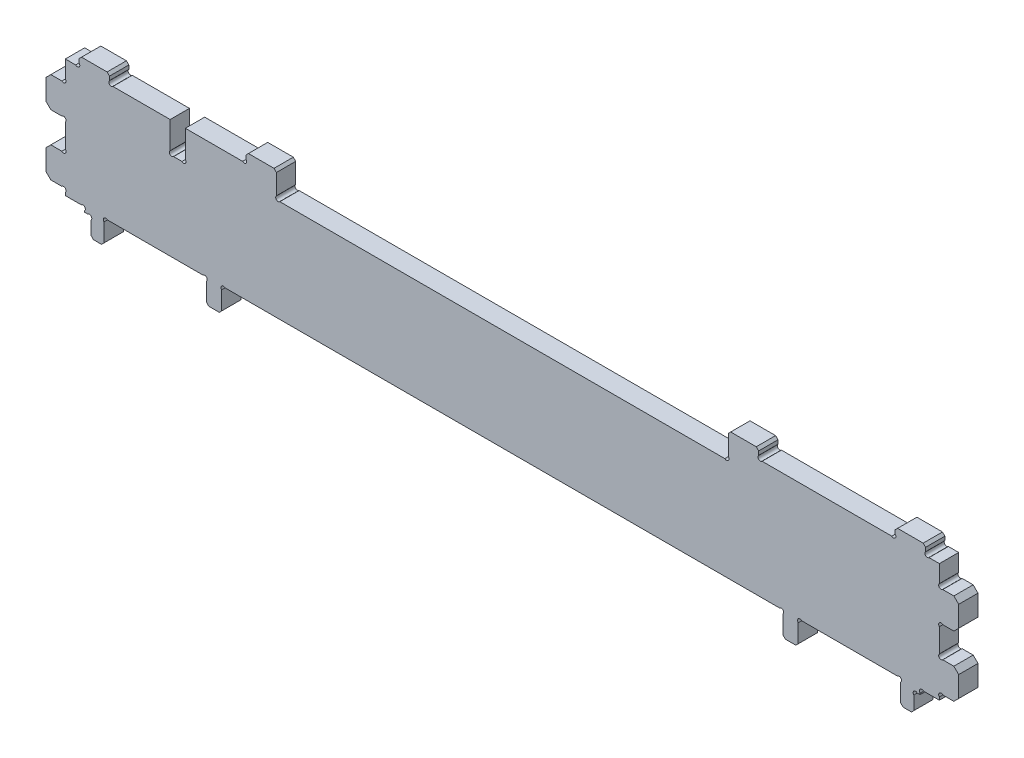
SolidWorks part; units mm, degrees
ref_plane "Front Plane" through (0, 0, 0) normal (0, 0, 1) x (1, 0, 0)
ref_plane "Top Plane" through (0, 0, 0) normal (0, 1, 0) x (1, 0, 0)
ref_plane "Right Plane" through (0, 0, 0) normal (1, 0, 0) x (0, 0, -1)
sketch "Sketch1" plane through (0, 0, 0) normal (0, 0, 1) x (1, 0, 0)
  line L69 (134.6215, -67.6125) -> (134.6215, -60.8103)
  line L70 (133.499, -59.6877) -> (102.0491, -59.6877)
  line L71 (100.9265, -60.8103) -> (100.9265, -67.6125)
  line L72 (100.9265, -67.6125) -> (95.9265, -67.6125)
  line L73 (95.9265, -67.6125) -> (95.9265, -60.8103)
  line L74 (94.804, -59.6877) -> (-87.4609, -59.6877)
  line L75 (-88.5835, -60.8103) -> (-88.5835, -67.6125)
  line L76 (-88.5835, -67.6125) -> (-93.5835, -67.6125)
  line L77 (-93.5835, -67.6125) -> (-93.5835, -60.8103)
  line L78 (-94.706, -59.6877) -> (-126.1559, -59.6877)
  line L79 (-127.2785, -60.8103) -> (-127.2785, -67.6125)
  line L80 (-127.2785, -67.6125) -> (-131.5077, -67.6125)
  line L81 (-131.5077, -67.6125) -> (-131.5077, -62.3851)
  line L82 (-132.6302, -61.2625) -> (-133.6285, -61.2625)
  line L83 (-133.6285, -61.2625) -> (-133.6285, -60.8103)
  line L84 (-134.751, -59.6877) -> (-139.9785, -59.6877)
  line L85 (-139.9785, -59.6877) -> (-139.9785, -58.7351)
  line L86 (-141.101, -57.6125) -> (-146.3285, -57.6125)
  line L87 (-146.3285, -57.6125) -> (-146.3285, -47.6125)
  line L88 (-146.3285, -47.6125) -> (-141.101, -47.6125)
  line L89 (-139.9785, -46.49) -> (-139.9785, -38.7351)
  line L90 (-141.101, -37.6125) -> (-146.3285, -37.6125)
  line L91 (-146.3285, -37.6125) -> (-146.3285, -27.6125)
  line L92 (-146.3285, -27.6125) -> (-141.101, -27.6125)
  line L93 (-139.9785, -26.49) -> (-139.9785, -20.7875)
  line L94 (-139.9785, -20.7875) -> (-136.576, -20.7875)
  line L95 (-135.4535, -19.665) -> (-135.4535, -17.6125)
  line L96 (-135.4535, -17.6125) -> (-125.4535, -17.6125)
  line L97 (-125.4535, -17.6125) -> (-125.4535, -19.665)
  line L98 (-124.3309, -20.7875) -> (-105.5215, -20.7875)
  line L99 (-105.5215, -20.7875) -> (-105.5215, -29.665)
  line L100 (-104.3989, -30.7875) -> (-101.644, -30.7875)
  line L101 (-100.5215, -29.665) -> (-100.5215, -20.7875)
  line L102 (-100.5215, -20.7875) -> (-81.712, -20.7875)
  line L103 (-80.5895, -19.665) -> (-80.5895, -17.6125)
  line L104 (-80.5895, -17.6125) -> (-70.5895, -17.6125)
  line L105 (-70.5895, -17.6125) -> (-70.5895, -24.1277)
  line L106 (-70.5895, -24.1277) -> (77.9325, -24.1277)
  line L107 (77.9325, -24.1277) -> (77.9325, -17.6125)
  line L108 (77.9325, -17.6125) -> (87.9325, -17.6125)
  line L109 (87.9325, -17.6125) -> (87.9325, -19.665)
  line L110 (89.0551, -20.7875) -> (131.674, -20.7875)
  line L111 (132.7965, -19.665) -> (132.7965, -17.6125)
  line L112 (132.7965, -17.6125) -> (142.7965, -17.6125)
  line L113 (142.7965, -17.6125) -> (142.7965, -19.665)
  line L114 (143.9191, -20.7875) -> (147.3215, -20.7875)
  line L115 (147.3215, -20.7875) -> (147.3215, -26.49)
  line L116 (148.4441, -27.6125) -> (153.6715, -27.6125)
  line L117 (153.6715, -27.6125) -> (153.6715, -37.6125)
  line L118 (153.6715, -37.6125) -> (148.4441, -37.6125)
  line L119 (147.3215, -38.7351) -> (147.3215, -46.49)
  line L120 (148.4441, -47.6125) -> (153.6715, -47.6125)
  line L121 (153.6715, -47.6125) -> (153.6715, -57.6125)
  line L122 (153.6715, -57.6125) -> (148.4441, -57.6125)
  line L123 (147.3215, -58.7351) -> (147.3215, -59.6877)
  line L124 (147.3215, -59.6877) -> (142.0941, -59.6877)
  line L125 (140.9715, -60.8103) -> (140.9715, -61.2625)
  line L126 (140.9715, -61.2625) -> (140.0715, -61.2625)
  line L127 (138.949, -62.3851) -> (138.949, -67.6125)
  line L128 (138.949, -67.6125) -> (134.6215, -67.6125)
  arc A28 (134.6215, -60.8103) -> (133.499, -59.6877) centre (134.0603, -60.249) ccw
  arc A29 (102.0491, -59.6877) -> (100.9265, -60.8103) centre (101.4878, -60.249) ccw
  arc A30 (95.9265, -60.8103) -> (94.804, -59.6877) centre (95.3653, -60.249) ccw
  arc A31 (-87.4609, -59.6877) -> (-88.5835, -60.8103) centre (-88.0222, -60.249) ccw
  arc A32 (-93.5835, -60.8103) -> (-94.706, -59.6877) centre (-94.1447, -60.249) ccw
  arc A33 (-126.1559, -59.6877) -> (-127.2785, -60.8103) centre (-126.7172, -60.249) ccw
  arc A34 (-131.5077, -62.3851) -> (-132.6302, -61.2625) centre (-132.069, -61.8238) ccw
  arc A35 (-133.6285, -60.8103) -> (-134.751, -59.6877) centre (-134.1897, -60.249) ccw
  arc A36 (-139.9785, -58.7351) -> (-141.101, -57.6125) centre (-140.5397, -58.1738) ccw
  arc A37 (-141.101, -47.6125) -> (-139.9785, -46.49) centre (-140.5397, -47.0513) ccw
  arc A38 (-139.9785, -38.7351) -> (-141.101, -37.6125) centre (-140.5397, -38.1738) ccw
  arc A39 (-141.101, -27.6125) -> (-139.9785, -26.49) centre (-140.5397, -27.0513) ccw
  arc A40 (-136.576, -20.7875) -> (-135.4535, -19.665) centre (-136.0147, -20.2263) ccw
  arc A41 (-125.4535, -19.665) -> (-124.3309, -20.7875) centre (-124.8922, -20.2263) ccw
  arc A42 (-105.5215, -29.665) -> (-104.3989, -30.7875) centre (-104.9602, -30.2263) ccw
  arc A43 (-101.644, -30.7875) -> (-100.5215, -29.665) centre (-101.0827, -30.2263) ccw
  arc A44 (-81.712, -20.7875) -> (-80.5895, -19.665) centre (-81.1507, -20.2263) ccw
  arc A47 (87.9325, -19.665) -> (89.0551, -20.7875) centre (88.4938, -20.2263) ccw
  arc A48 (131.674, -20.7875) -> (132.7965, -19.665) centre (132.2353, -20.2263) ccw
  arc A49 (142.7965, -19.665) -> (143.9191, -20.7875) centre (143.3578, -20.2263) ccw
  arc A50 (147.3215, -26.49) -> (148.4441, -27.6125) centre (147.8828, -27.0513) ccw
  arc A51 (148.4441, -37.6125) -> (147.3215, -38.7351) centre (147.8828, -38.1738) ccw
  arc A52 (147.3215, -46.49) -> (148.4441, -47.6125) centre (147.8828, -47.0513) ccw
  arc A53 (148.4441, -57.6125) -> (147.3215, -58.7351) centre (147.8828, -58.1738) ccw
  arc A54 (142.0941, -59.6877) -> (140.9715, -60.8103) centre (141.5328, -60.249) ccw
  arc A55 (140.0715, -61.2625) -> (138.949, -62.3851) centre (139.5102, -61.8238) ccw
  point P0 (-70.1985, -24.1277)
  dimension "D1" = 38.9002
extrude "Boss-Extrude1" add sketch "Sketch1" along normal blind 6.35
sketch "Sketch2" plane through (0, 0, 6.35) normal (0, 0, 1) x (1, 0, 0)
  line L0 (-87.4609, -59.6877) -> (94.804, -59.6877) construction
  line L1 (-70.5895, -24.1277) -> (77.9325, -24.1277)
  line L2 (-70.5895, -24.1277) -> (-70.5895, -26.1597)
  line L3 (-70.5895, -26.1597) -> (77.9325, -26.1597)
  line L4 (77.9325, -24.1277) -> (77.9325, -26.1597)
  dimension "D1" = 33.528
extrude "Cut-Extrude1" cut sketch "Sketch2" against normal through all
sketch "Sketch3" plane through (0, 0, 6.35) normal (0, 0, 1) x (1, 0, 0)
  line L0 (-70.5895, -26.1597) -> (-69.4669, -26.1597) construction
  line L1 (-70.5895, -26.1597) -> (77.9325, -26.1597) construction
  line L2 (-70.5895, -25.0372) -> (-70.5895, -26.1597) construction
  line L3 (-70.5895, -26.1597) -> (-70.5895, -17.6125) construction
  line L4 (3.6715, -26.1597) -> (3.6715, -59.6877) construction
  line L5 (-87.4609, -59.6877) -> (94.804, -59.6877) construction
  line L6 (77.9325, -25.0372) -> (77.9325, -26.1597) construction
  line L7 (77.9325, -26.1597) -> (76.81, -26.1597) construction
  circle A0 centre (-70.0282, -25.5985) radius 0.7937
  circle A1 centre (77.3713, -25.5985) radius 0.7937
  dimension "D1" = 1.5875
extrude "Cut-Extrude2" cut sketch "Sketch3" against normal through all
chamfer "Chamfer1" distance 0.7937 angle 45 16 edges at (-131.5077, -67.6125, 3.175) (-93.5835, -67.6125, 3.175) (-127.2785, -67.6125, 3.175) (-88.5835, -67.6125, 3.175) (100.9265, -67.6125, 3.175) (95.9265, -67.6125, 3.175) (134.6215, -67.6125, 3.175) (138.949, -67.6125, 3.175) (132.7965, -17.6125, 3.175) (142.7965, -17.6125, 3.175) (87.9325, -17.6125, 3.175) (77.9325, -17.6125, 3.175) (-70.5895, -17.6125, 3.175) (-80.5895, -17.6125, 3.175) (-125.4535, -17.6125, 3.175) (-135.4535, -17.6125, 3.175)
chamfer "Chamfer2" distance 1.5875 angle 45 8 edges at (153.6715, -57.6125, 3.175) (153.6715, -47.6125, 3.175) (153.6715, -37.6125, 3.175) (153.6715, -27.6125, 3.175) (-146.3285, -57.6125, 3.175) (-146.3285, -47.6125, 3.175) (-146.3285, -37.6125, 3.175) (-146.3285, -27.6125, 3.175)
